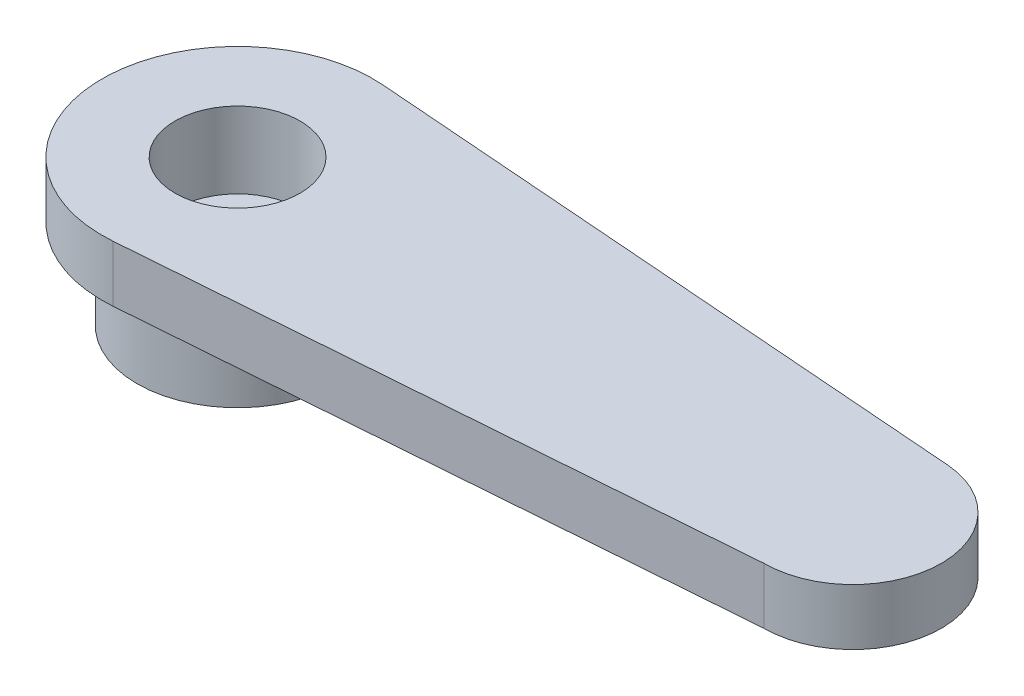
SolidWorks part; units mm, degrees
ref_plane "Plano frontal" through (0, 0, 0) normal (0, 0, 1) x (1, 0, 0)
ref_plane "Plano superior" through (0, 0, 0) normal (0, 1, 0) x (1, 0, 0)
ref_plane "Plano direito" through (0, 0, 0) normal (1, 0, 0) x (0, 0, -1)
sketch "Esboço1" plane through (0, 0, 0) normal (0, 1, 0) x (1, 0, 0)
  line L0 (0, 0) -> (29.5, 0) construction
  line L1 (0.4958, 6.4811) -> (29.8242, 4.2376)
  line L2 (0.4985, -6.4809) -> (29.5, -4.25)
  arc A0 (29.5, -4.25) -> (29.8242, 4.2376) centre (29.5, 0) ccw
  arc A1 (0.4958, 6.4811) -> (0.4985, -6.4809) centre (0, 0) ccw
  circle A2 centre (0, 0) radius 3
  circle A3 centre (0, 0) radius 4.825
  dimension "D1" = 29.5
  dimension "D2" = 8.5
  dimension "D3" = 13
  dimension "D4" = 6
  dimension "D5" = 9.65
extrude "Ressalto-extrusão1" add sketch "Esboço1" along normal blind 2.7 contours L1 A0 L2 A1
extrude "Ressalto-extrusão2" add sketch "Esboço1<6>" against normal blind 4.3 contours A3
sketch "Esboço1<6>" plane through (0, 0, 0) normal (0, 1, 0) x (1, 0, 0) same geometry as "Esboço1"
sketch "Esboço4" plane through (0, 2.7, 0) normal (0, 1, 0) x (1, 0, 0)
  circle A0 centre (0, 0) radius 3 construction
  circle A1 centre (0, 0) radius 3
extrude "Corte-extrusão1" cut sketch "Esboço4" against normal blind 3.65
sketch "Esboço5" plane through (0, -0.95, 0) normal (0, 1, 0) x (1, 0, 0)
  circle A0 centre (0, 0) radius 2
  dimension "D1" = 4
extrude "Corte-extrusão2" cut sketch "Esboço5" against normal blind 3.65
